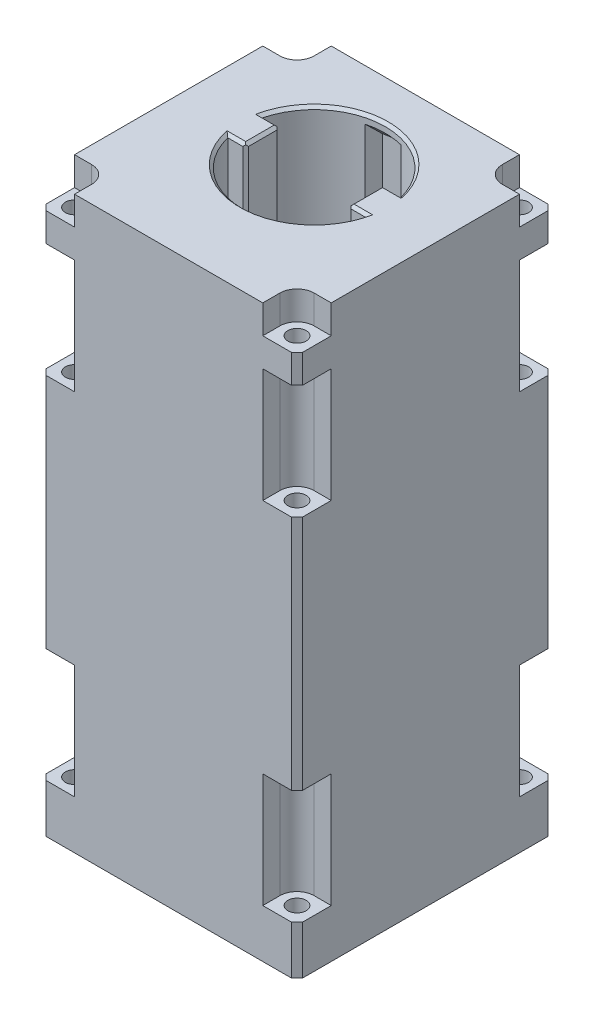
SolidWorks part; units mm, degrees
ref_plane "前视基准面" through (0, 0, 0) normal (0, 0, 1) x (1, 0, 0)
ref_plane "上视基准面" through (0, 0, 0) normal (0, 1, 0) x (1, 0, 0)
ref_plane "右视基准面" through (0, 0, 0) normal (1, 0, 0) x (0, 0, -1)
sketch "草图1" plane through (0, 0, 0) normal (0, 1, 0) x (1, 0, 0)
  line L1 (-22.5, -19.5) -> (22.5, -19.5)
  line L2 (-22.5, -19.5) -> (-22.5, 19.5)
  line L3 (-22.5, 19.5) -> (22.5, 19.5)
  line L4 (22.5, -19.5) -> (22.5, 19.5)
  line L5 (-22.5, -19.5) -> (22.5, 19.5) construction
  line L6 (-22.5, 19.5) -> (22.5, -19.5) construction
  circle A0 centre (0, 0) radius 12.5
  point P0 (0, 0)
  dimension "D3" = 25
  dimension "D1" = 39
  dimension "D2" = 45
extrude "凸台-拉伸1" add sketch "草图1" along normal blind 100
sketch "草图2" plane through (0, 100, 0) normal (0, 1, 0) x (1, 0, 0)
  line L1 (0, 0) -> (12, 0) construction
  line L3 (9, 3) -> (15, 3)
  line L4 (9, 3) -> (9, -3)
  line L5 (9, -3) -> (15, -3)
  line L6 (15, 3) -> (15, -3)
  line L7 (9, 3) -> (15, -3) construction
  line L8 (9, -3) -> (15, 3) construction
  line L12 (-9, -3) -> (-9, 3)
  line L13 (-9, -3) -> (-15, -3)
  line L14 (-15, -3) -> (-15, 3)
  line L15 (-9, 3) -> (-15, 3)
  point P3 (12, 0)
  point P24 (0, 0)
  dimension "D1" = 6
  dimension "D2" = 6
  dimension "D4" = 12
  dimension "D3" = 2
extrude "凸台-拉伸2" add sketch "草图2" against normal blind 100
sketch "草图3" plane through (0, 0, 19.5) normal (0, 0, 1) x (1, 0, 0)
  line L4 (-22.5, 0) -> (22.5, 0)
  line L5 (22.5, 0) -> (22.5, 100)
  line L6 (22.5, 100) -> (-22.5, 100)
  line L7 (-22.5, 100) -> (-22.5, 0)
  line L8 (-22.5, 0) -> (22.5, 0)
  line L9 (22.5, 0) -> (22.5, 100)
  line L10 (22.5, 100) -> (-22.5, 100)
  line L11 (-22.5, 100) -> (-22.5, 0)
  dimension "D1" = 0
extrude "凸台-拉伸3" add sketch "草图3" along normal blind 6
sketch "草图4" plane through (0, 100, 0) normal (0, 1, 0) x (1, 0, 0)
  line L0 (-22.5, 19.5) -> (-22.5, -25.5) construction
  line L1 (22.5, 19.5) -> (-22.5, 19.5) construction
  line L4 (0, 19.5) -> (0, -25.5) construction
  line L7 (22.5, -25.5) -> (-22.5, -25.5) construction
  line L8 (-22.5, -3) -> (22.5, -3) construction
  line L9 (22.5, -25.5) -> (22.5, 19.5) construction
  circle A1 centre (-19.5, 16.5) radius 1.6
  circle A4 centre (19.5, 16.5) radius 1.6
  circle A5 centre (19.5, -22.5) radius 1.6
  circle A6 centre (-19.5, -22.5) radius 1.6
  dimension "D6" = 3.2
  dimension "D1" = 3
  dimension "D2" = 3
extrude "切除-拉伸1" cut sketch "草图4" against normal through all
sketch "草图5" plane through (0, 100, 0) normal (0, 1, 0) x (1, 0, 0)
  line L9 (-19.5, 13.5) -> (-22.5, 13.5)
  line L10 (-22.5, 19.5) -> (-22.5, -25.5) construction
  line L11 (-22.5, 13.5) -> (-22.5, 19.5)
  line L12 (-22.5, 19.5) -> (-16.5, 19.5)
  line L13 (22.5, 19.5) -> (-22.5, 19.5) construction
  line L14 (-16.5, 19.5) -> (-16.5, 16.5)
  line L15 (0, 19.5) -> (0, -25.5) construction
  line L28 (22.5, -25.5) -> (-22.5, -25.5) construction
  line L29 (-22.5, -3) -> (22.5, -3) construction
  line L30 (22.5, -25.5) -> (22.5, 19.5) construction
  line L31 (22.5, 19.5) -> (16.5, 19.5)
  line L32 (22.5, 13.5) -> (22.5, 19.5)
  line L33 (19.5, 13.5) -> (22.5, 13.5)
  line L34 (16.5, 19.5) -> (16.5, 16.5)
  line L35 (22.5, -19.5) -> (22.5, -25.5)
  line L36 (19.5, -19.5) -> (22.5, -19.5)
  line L37 (16.5, -25.5) -> (16.5, -22.5)
  line L39 (22.5, -25.5) -> (16.5, -25.5)
  line L40 (-22.5, -25.5) -> (-16.5, -25.5)
  line L41 (-22.5, -19.5) -> (-22.5, -25.5)
  line L42 (-19.5, -19.5) -> (-22.5, -19.5)
  line L43 (-16.5, -25.5) -> (-16.5, -22.5)
  arc A4 (-16.5, 16.5) -> (-19.5, 13.5) centre (-19.5, 16.5) cw
  arc A5 (16.5, 16.5) -> (19.5, 13.5) centre (19.5, 16.5) ccw
  arc A7 (16.5, -22.5) -> (19.5, -19.5) centre (19.5, -22.5) cw
  arc A8 (-16.5, -22.5) -> (-19.5, -19.5) centre (-19.5, -22.5) ccw
  dimension "D1" = 3
extrude "切除-拉伸2" cut sketch "草图5" against normal blind 5
ref_plane "基准面1" through (0, 90, 0) normal (0, 1, 0) x (1, 0, 0)
sketch "草图8" plane through (0, 90, 0) normal (0, 1, 0) x (1, 0, 0)
  line L9 (-22.5, 13.5) -> (-19.5, 13.5)
  line L15 (-22.5, 19.5) -> (-22.5, 13.5)
  line L16 (-16.5, 19.5) -> (-22.5, 19.5)
  line L17 (-16.5, 16.5) -> (-16.5, 19.5)
  line L27 (-22.5, 13.5) -> (-19.5, 13.5)
  line L28 (-22.5, 19.5) -> (-22.5, 13.5)
  line L29 (-16.5, 19.5) -> (-22.5, 19.5)
  line L35 (-16.5, 16.5) -> (-16.5, 19.5)
  line L100 (22.5, 19.5) -> (16.5, 19.5)
  line L101 (16.5, 19.5) -> (16.5, 16.5)
  line L102 (19.5, 13.5) -> (22.5, 13.5)
  line L103 (22.5, 13.5) -> (22.5, 19.5)
  line L108 (22.5, 19.5) -> (16.5, 19.5)
  line L109 (16.5, 19.5) -> (16.5, 16.5)
  line L110 (19.5, 13.5) -> (22.5, 13.5)
  line L111 (22.5, 13.5) -> (22.5, 19.5)
  line L116 (-22.5, -25.5) -> (-16.5, -25.5)
  line L117 (-16.5, -25.5) -> (-16.5, -22.5)
  line L118 (-19.5, -19.5) -> (-22.5, -19.5)
  line L119 (-22.5, -19.5) -> (-22.5, -25.5)
  line L120 (-22.5, -25.5) -> (-16.5, -25.5)
  line L121 (-16.5, -25.5) -> (-16.5, -22.5)
  line L122 (-19.5, -19.5) -> (-22.5, -19.5)
  line L123 (-22.5, -19.5) -> (-22.5, -25.5)
  line L124 (16.5, -22.5) -> (16.5, -25.5)
  line L125 (22.5, -19.5) -> (19.5, -19.5)
  line L126 (22.5, -25.5) -> (22.5, -19.5)
  line L127 (16.5, -25.5) -> (22.5, -25.5)
  line L128 (16.5, -22.5) -> (16.5, -25.5)
  line L129 (22.5, -19.5) -> (19.5, -19.5)
  line L130 (22.5, -25.5) -> (22.5, -19.5)
  line L131 (16.5, -25.5) -> (22.5, -25.5)
  arc A3 (-19.5, 13.5) -> (-16.5, 16.5) centre (-19.5, 16.5) ccw
  arc A7 (-19.5, 13.5) -> (-16.5, 16.5) centre (-19.5, 16.5) ccw
  arc A21 (16.5, 16.5) -> (19.5, 13.5) centre (19.5, 16.5) ccw
  arc A23 (16.5, 16.5) -> (19.5, 13.5) centre (19.5, 16.5) ccw
  arc A25 (-16.5, -22.5) -> (-19.5, -19.5) centre (-19.5, -22.5) ccw
  arc A26 (-16.5, -22.5) -> (-19.5, -19.5) centre (-19.5, -22.5) ccw
  arc A27 (19.5, -19.5) -> (16.5, -22.5) centre (19.5, -22.5) ccw
  arc A28 (19.5, -19.5) -> (16.5, -22.5) centre (19.5, -22.5) ccw
  dimension "D1" = 0
  dimension "D2" = 0
  dimension "D3" = 0
  dimension "D4" = 0
extrude "切除-拉伸4" cut sketch "草图8" against normal blind 20
ref_plane "基准面2" through (0, 50, 0) normal (0, 1, 0) x (1, 0, 0)
sketch "草图9" plane through (0, 0, 0) normal (0, -1, 0) x (1, 0, 0)
  line L0 (0, 0) -> (0, 12) construction
  line L1 (-9, 0) -> (9, 0) construction
  line L6 (-3.15, 15.15) -> (3.15, 15.15)
  line L7 (-3.15, 15.15) -> (-3.15, 8.85)
  line L8 (-3.15, 8.85) -> (3.15, 8.85)
  line L9 (3.15, 15.15) -> (3.15, 8.85)
  line L10 (-3.15, 15.15) -> (3.15, 8.85) construction
  line L11 (-3.15, 8.85) -> (3.15, 15.15) construction
  line L12 (-9, 3) -> (-9, -3) construction
  line L13 (9, -3) -> (9, 3) construction
  line L14 (-3.15, -8.85) -> (3.15, -8.85)
  line L15 (3.15, -15.15) -> (3.15, -8.85)
  line L16 (-3.15, -15.15) -> (3.15, -15.15)
  line L17 (-3.15, -15.15) -> (-3.15, -8.85)
  dimension "D1" = 6.3
  dimension "D2" = 6.3
  dimension "D3" = 12
extrude "切除-拉伸5" cut sketch "草图9" against normal blind 95
ref_plane "基准面3" through (0, 8.5, 0) normal (0, -1, 0) x (-1, 0, 0)
sketch "草图10" plane through (0, 8.5, 0) normal (0, -1, 0) x (-1, 0, 0)
  line L4 (-16.5, 19.5) -> (-22.5, 19.5)
  line L5 (-16.5, 16.5) -> (-16.5, 19.5)
  line L6 (-22.5, 13.5) -> (-19.5, 13.5)
  line L7 (-22.5, 19.5) -> (-22.5, 13.5)
  line L8 (-16.5, 19.5) -> (-22.5, 19.5)
  line L9 (-16.5, 16.5) -> (-16.5, 19.5)
  line L10 (-22.5, 13.5) -> (-19.5, 13.5)
  line L11 (-22.5, 19.5) -> (-22.5, 13.5)
  line L12 (19.5, 13.5) -> (22.5, 13.5)
  line L13 (16.5, 19.5) -> (16.5, 16.5)
  line L14 (22.5, 19.5) -> (16.5, 19.5)
  line L15 (22.5, 13.5) -> (22.5, 19.5)
  line L16 (19.5, 13.5) -> (22.5, 13.5)
  line L17 (16.5, 19.5) -> (16.5, 16.5)
  line L18 (22.5, 19.5) -> (16.5, 19.5)
  line L19 (22.5, 13.5) -> (22.5, 19.5)
  line L20 (-16.5, -25.5) -> (-16.5, -22.5)
  line L21 (-22.5, -25.5) -> (-16.5, -25.5)
  line L22 (-22.5, -19.5) -> (-22.5, -25.5)
  line L23 (-19.5, -19.5) -> (-22.5, -19.5)
  line L24 (-16.5, -25.5) -> (-16.5, -22.5)
  line L25 (-22.5, -25.5) -> (-16.5, -25.5)
  line L26 (-22.5, -19.5) -> (-22.5, -25.5)
  line L27 (-19.5, -19.5) -> (-22.5, -19.5)
  line L28 (22.5, -19.5) -> (19.5, -19.5)
  line L29 (22.5, -25.5) -> (22.5, -19.5)
  line L30 (16.5, -25.5) -> (22.5, -25.5)
  line L31 (16.5, -22.5) -> (16.5, -25.5)
  line L32 (22.5, -19.5) -> (19.5, -19.5)
  line L33 (22.5, -25.5) -> (22.5, -19.5)
  line L34 (16.5, -25.5) -> (22.5, -25.5)
  line L35 (16.5, -22.5) -> (16.5, -25.5)
  arc A1 (-19.5, 13.5) -> (-16.5, 16.5) centre (-19.5, 16.5) ccw
  arc A2 (-19.5, 13.5) -> (-16.5, 16.5) centre (-19.5, 16.5) ccw
  arc A3 (16.5, 16.5) -> (19.5, 13.5) centre (19.5, 16.5) ccw
  arc A4 (16.5, 16.5) -> (19.5, 13.5) centre (19.5, 16.5) ccw
  arc A5 (-16.5, -22.5) -> (-19.5, -19.5) centre (-19.5, -22.5) ccw
  arc A6 (-16.5, -22.5) -> (-19.5, -19.5) centre (-19.5, -22.5) ccw
  arc A7 (19.5, -19.5) -> (16.5, -22.5) centre (19.5, -22.5) ccw
  arc A8 (19.5, -19.5) -> (16.5, -22.5) centre (19.5, -22.5) ccw
  dimension "D1" = 0
  dimension "D2" = 0
  dimension "D3" = 0
  dimension "D4" = 0
extrude "切除-拉伸6" cut sketch "草图10" against normal blind 20
chamfer "倒角1" distance 1 angle 45 12 edges at (22.5, 4.25, 25.5) (22.5, 4.25, -19.5) (-22.5, 4.25, 25.5) (-22.5, 4.25, -19.5) (-22.5, 92.5, 25.5) (-22.5, 49.25, 25.5) (22.5, 92.5, 25.5) (22.5, 49.25, 25.5) (-22.5, 92.5, -19.5) (22.5, 92.5, -19.5) (-22.5, 49.25, -19.5) (22.5, 49.25, -19.5)
chamfer "倒角2" distance 0.5 angle 45 24 edges at (10.5673, 100, -3) (9, 100, 0) (10.5673, 100, 3) (0, 100, 12.5) (-10.5673, 100, 3) (-9, 100, 0) (-10.5673, 100, -3) (0, 100, -12.5) (3.15, 0, 13.6233) (0, 0, 15.15) (-3.15, 0, 13.6233) (-8.8934, 0, 8.784) (-10.5673, 0, 3) (-9, 0, 0) (-10.5673, 0, -3) (-8.8934, 0, -8.784) (-3.15, 0, -13.6233) (0, 0, -15.15) (3.15, 0, -13.6233) (8.8934, 0, -8.784) (8.8934, 0, 8.784) (10.5673, 0, 3) (9, 0, 0) (10.5673, 0, -3)
chamfer "倒角3" distance 0.5 angle 45 4 edges at (9, 50, 3) (9, 50, -3) (-9, 50, 3) (-9, 50, -3)
chamfer "倒角4" distance 3.5 angle 45 2 edges at (0, 95, 12.5) (0, 95, -12.5)
